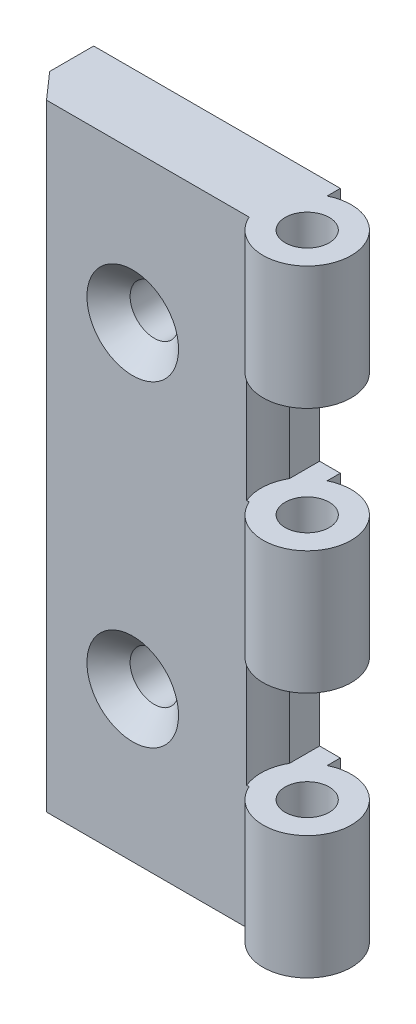
SolidWorks part; units mm, degrees
ref_plane "Front Plane" through (0, 0, 0) normal (0, 0, 1) x (1, 0, 0)
ref_plane "Top Plane" through (0, 0, 0) normal (0, 1, 0) x (1, 0, 0)
ref_plane "Right Plane" through (0, 0, 0) normal (1, 0, 0) x (0, 0, -1)
sketch "Sketch1" plane through (0, 0, 0) normal (0, 1, 0) x (1, 0, 0)
  line L0 (0, 0) -> (28, 0)
  line L1 (28, 0) -> (28, -1.5)
  line L2 (0, 0) -> (0, -5)
  line L3 (0, -5) -> (2.6458, -8)
  line L4 (2.6458, -8) -> (25.6458, -8)
  arc A0 (25.6458, -8) -> (28, -1.5) centre (30.2197, -5.9803) ccw
  circle A1 centre (30.2197, -5.9803) radius 2.5
  dimension "D1" = 28
  dimension "D6" = 10
  dimension "D8" = 5
  dimension "D2" = 5
  dimension "D3" = 4
  dimension "D4" = 23
  dimension "D5" = 8
  dimension "D7" = 1.5
extrude "Boss-Extrude1" add sketch "Sketch1" along normal mid plane 70
sketch "Sketch2" plane through (0, 0, 0) normal (0, 0, 1) x (1, 0, 0)
  line L0 (35.2197, -35) -> (35.2197, 35) construction
  line L1 (44.7936, 21) -> (25.6458, 21)
  line L2 (44.7936, 21) -> (44.7936, 7)
  line L3 (44.7936, 7) -> (25.6458, 7)
  line L4 (25.6458, 21) -> (25.6458, 7)
  line L5 (35.2197, 7) -> (35.2197, 21) construction
  line L6 (44.7936, 14) -> (25.6458, 14) construction
  line L7 (25.6458, 35) -> (25.6458, -35) construction
  line L8 (35.2197, -35) -> (35.2197, -21) construction
  line L9 (44.7936, -7) -> (25.6458, -7)
  line L10 (44.7936, -7) -> (44.7936, -21)
  line L11 (44.7936, -21) -> (25.6458, -21)
  line L12 (25.6458, -7) -> (25.6458, -21)
  line L13 (35.2197, -21) -> (35.2197, -7) construction
  line L14 (44.7936, -14) -> (25.6458, -14) construction
  line L15 (35.2197, -35) -> (35.2197, 35) construction
  line L16 (35.2197, 7) -> (35.2197, -7) construction
  line L17 (35.2197, 35) -> (35.2197, 21) construction
  point P0 (35.2197, 14)
  point P11 (35.2197, -14)
extrude "Cut-Extrude1" cut sketch "Sketch2" along normal through all both and the other way through all
hole_wizard "CSK for M5 Flat Head Machine Screw1" positions "Sketch4" profile "Sketch5" countersink size "M5" standard "ANSI Metric"
sketch "Sketch4" plane through (0, 0, 8) normal (0, 0, 1) x (1, 0, 0)
  line L0 (12.4327, -18) -> (12.4327, -35) construction
  line L3 (12.4327, 18) -> (12.4327, 35) construction
  line L4 (2.6458, 35) -> (25.6458, 35) construction
  line L5 (2.6458, -35) -> (25.6458, -35) construction
  line L6 (30.4327, 35) -> (30.4327, 21) construction
  line L7 (35.2197, 35) -> (25.6458, 35) construction
  line L8 (25.6458, 21) -> (35.2197, 21) construction
  point P0 (12.4327, 18)
  point P2 (12.4327, -18)
  dimension "D1" = 36
  dimension "D2" = 18
sketch "Sketch5" plane through (12.4327, 18, 8) normal (1, 0, 0) x (0, -1, 0)
  line L0 (0, 0) -> (0, 15)
  line L1 (0, 15) -> (2.75, 13.3476)
  line L2 (2.75, 13.3476) -> (2.75, 2.45)
  line L3 (2.75, 2.45) -> (5.2, 0)
  line L5 (5.2, 0) -> (0, 0)
  line L6 (-2.75, 2.45) -> (-5.2, 0) construction
  line L10 (0, 15) -> (-2.75, 13.3476) construction
  line L11 (0, -6.35) -> (0, 107.95) construction
  dimension "Hole Dia." = 5.5
  dimension "Hole Depth" = 15
  dimension "Near C'Sink Dia." = 10.4
  dimension "Near C'Sink Angle" = 90
  dimension "Drill Angle" = 118
sketch "Sketch6" plane through (0, 35, 0) normal (0, 1, 0) x (1, 0, 0)
  circle A0 centre (30.2197, -5.9803) radius 5.25
  dimension "D1" = 10.5
extrude "Cut-Extrude2" cut sketch "Sketch6" against normal up to surface (28 mm away) from surface up to face at (30.2197, 7, 8.4803) starting at face at (30.2197, 21, 3.4803)
extrude "Cut-Extrude3" cut sketch "Sketch6<2>" against normal up to surface (56 mm away) from surface up to face at (30.2197, -21, 8.4803) starting at face at (30.2197, -7, 3.4803)
sketch "Sketch6<2>" plane through (0, 35, 0) normal (0, 1, 0) x (1, 0, 0) same geometry as "Sketch6"
